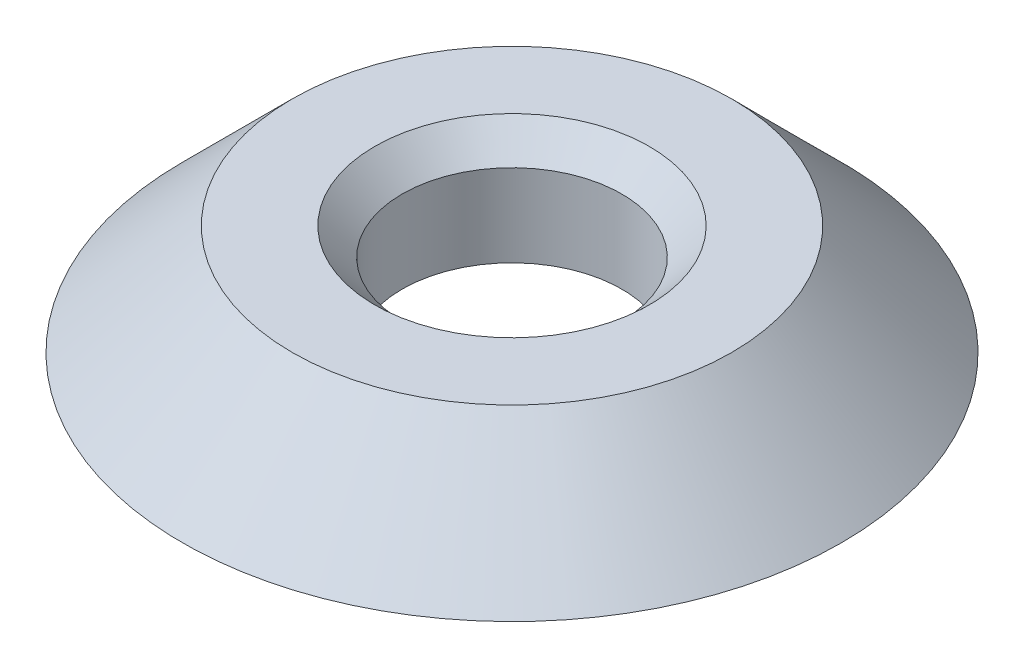
SolidWorks part; units mm, degrees
ref_plane "Front Plane" through (0, 0, 0) normal (0, 0, 1) x (1, 0, 0)
ref_plane "Top Plane" through (0, 0, 0) normal (0, 1, 0) x (1, 0, 0)
ref_plane "Right Plane" through (0, 0, 0) normal (1, 0, 0) x (0, 0, -1)
sketch "Sketch1" plane through (0, 0, 0) normal (0, 0, 1) x (1, 0, 0)
  line L0 (0, -795.7279) -> (0, 38990.6679) construction
  line L1 (2, 0) -> (2, 2)
  line L2 (2, 2) -> (4, 2)
  line L5 (4, 2) -> (6, 0)
  line L6 (6, 0) -> (2, 0)
  point P6 (4.6617, 4.2341)
  point P7 (3.5578, 2)
  point P8 (0, 0)
  point P10 (4.8374, 5.8625)
  point P11 (0, 0)
  point P12 (4.4625, 5)
  dimension "D1" = 4
  dimension "D2" = 8
  dimension "D3" = 12
  dimension "D5" = 2
revolve "Revolve1" add sketch "Sketch1" angle 360 about L0
chamfer "Chamfer1" distance 0.5 angle 45 1 edges at (2, 2, 0)
